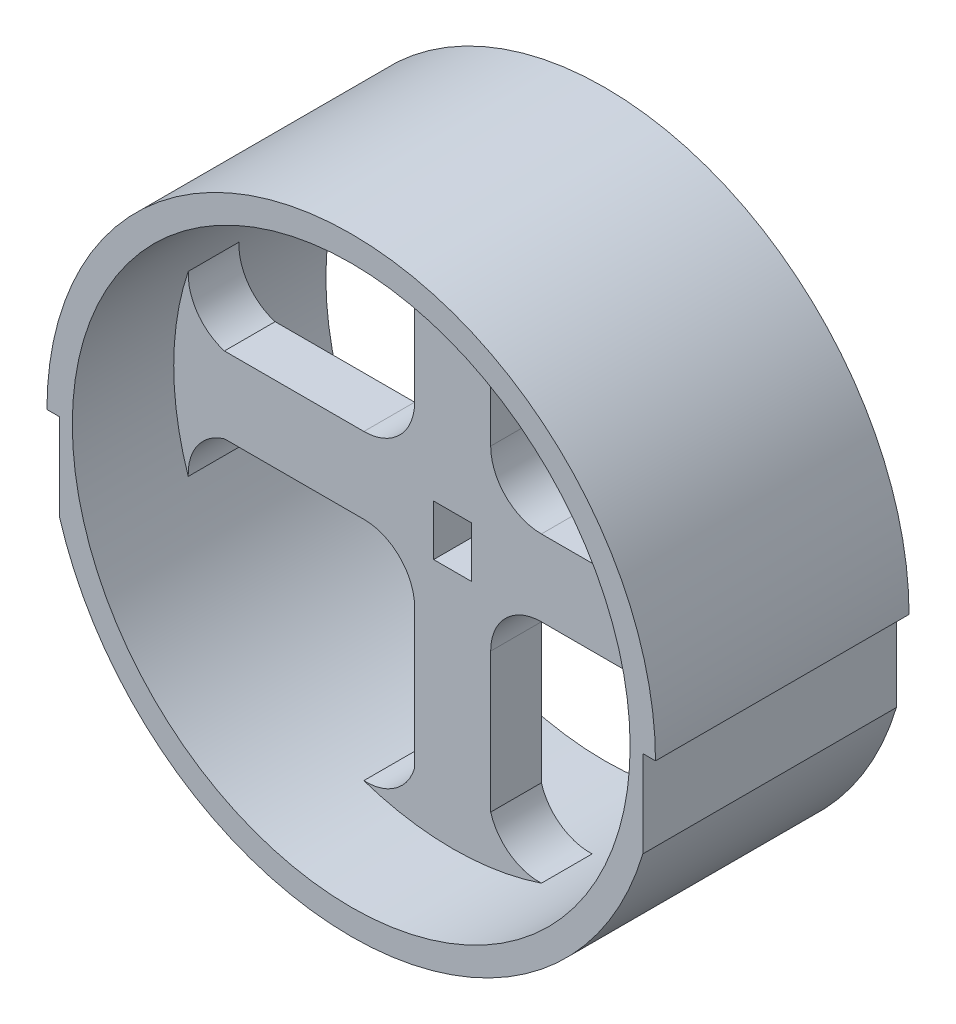
SolidWorks part; units mm, degrees
material "6061 Alloy"
ref_plane "Front Plane" through (0, 0, 0) normal (0, 0, 1) x (1, 0, 0)
ref_plane "Top Plane" through (0, 0, 0) normal (0, 1, 0) x (1, 0, 0)
ref_plane "Right Plane" through (0, 0, 0) normal (1, 0, 0) x (0, 0, -1)
sketch "Sketch1" plane through (0, 0, 0) normal (0, 0, 1) x (1, 0, 0)
  circle A0 centre (0, 0) radius 152.4
  circle A1 centre (0, 0) radius 139.7
  dimension "D1" = 304.8
  dimension "D2" = 279.4
extrude "Boss-Extrude1" add sketch "Sketch1" along normal mid plane 127
sketch "Sketch2" plane through (0, 0, 0) normal (0, 0, 1) x (1, 0, 0)
  line L0 (-114.3, 19.05) -> (-138.7192, 19.05)
  line L1 (-147.1918, -19.05) -> (147.1918, -19.05)
  line L2 (-147.1918, -19.05) -> (-147.1918, 19.05)
  line L3 (-147.1918, 19.05) -> (147.1918, 19.05)
  line L4 (147.1918, -19.05) -> (147.1918, 19.05)
  line L5 (-147.1918, -19.05) -> (147.1918, 19.05) construction
  line L6 (-147.1918, 19.05) -> (147.1918, -19.05) construction
  line L7 (19.05, -143.9568) -> (-19.05, -143.9568)
  line L8 (19.05, -143.9568) -> (19.05, 143.9568)
  line L9 (19.05, 143.9568) -> (-19.05, 143.9568)
  line L10 (-19.05, -143.9568) -> (-19.05, 143.9568)
  line L11 (19.05, -143.9568) -> (-19.05, 143.9568) construction
  line L12 (19.05, 143.9568) -> (-19.05, -143.9568) construction
  line L15 (-44.45, 19.05) -> (-19.05, 19.05)
  line L16 (-19.05, 44.45) -> (-19.05, 19.05)
  line L17 (-132.4254, 44.4927) -> (-143.3503, 19.05)
  line L18 (-143.3503, 19.05) -> (-138.7192, 19.05)
  line L19 (-138.7192, 19.05) -> (-143.3503, 19.05)
  line L20 (-19.05, 114.3) -> (-19.05, 143.9568)
  line L21 (-44.45, 132.4398) -> (-19.05, 143.9568)
  line L22 (44.45, 19.05) -> (19.05, 19.05)
  line L23 (19.05, 44.45) -> (19.05, 19.05)
  line L24 (19.05, 143.3503) -> (19.05, 138.7192)
  line L25 (19.05, 114.3) -> (19.05, 138.7192)
  line L26 (44.4927, 132.4254) -> (19.05, 143.3503)
  line L27 (114.3, 19.05) -> (143.9568, 19.05)
  line L28 (132.4398, 44.45) -> (143.9568, 19.05)
  line L29 (19.05, -44.45) -> (19.05, -19.05)
  line L30 (44.45, -19.05) -> (19.05, -19.05)
  line L31 (143.3503, -19.05) -> (138.7192, -19.05)
  line L32 (114.3, -19.05) -> (138.7192, -19.05)
  line L33 (132.4254, -44.4927) -> (143.3503, -19.05)
  line L34 (19.05, -114.3) -> (19.05, -143.9568)
  line L35 (44.45, -132.4398) -> (19.05, -143.9568)
  line L36 (-44.45, -19.05) -> (-19.05, -19.05)
  line L37 (-19.05, -44.45) -> (-19.05, -19.05)
  line L38 (-19.05, -143.3503) -> (-19.05, -138.7192)
  line L39 (-19.05, -114.3) -> (-19.05, -138.7192)
  line L40 (-44.4927, -132.4254) -> (-19.05, -143.3503)
  line L41 (-114.3, -19.05) -> (-143.9568, -19.05)
  line L42 (-132.4398, -44.45) -> (-143.9568, -19.05)
  arc A1 (-44.45, 19.05) -> (-19.05, 44.45) centre (-44.45, 44.45) ccw
  arc A2 (-114.3, 19.05) -> (-132.4254, 44.4927) centre (-107.0492, 43.3931) cw
  circle A3 centre (0, 0) radius 139.7 construction
  arc A5 (-19.05, 114.3) -> (-44.45, 132.4398) centre (-43.3968, 107.0616) ccw
  arc A6 (19.05, 44.45) -> (44.45, 19.05) centre (44.45, 44.45) ccw
  arc A7 (19.05, 114.3) -> (44.4927, 132.4254) centre (43.3931, 107.0492) cw
  arc A8 (114.3, 19.05) -> (132.4398, 44.45) centre (107.0616, 43.3968) ccw
  arc A9 (44.45, -19.05) -> (19.05, -44.45) centre (44.45, -44.45) ccw
  arc A10 (114.3, -19.05) -> (132.4254, -44.4927) centre (107.0492, -43.3931) cw
  arc A11 (19.05, -114.3) -> (44.45, -132.4398) centre (43.3968, -107.0616) ccw
  arc A12 (-19.05, -44.45) -> (-44.45, -19.05) centre (-44.45, -44.45) ccw
  arc A13 (-19.05, -114.3) -> (-44.4927, -132.4254) centre (-43.3931, -107.0492) cw
  arc A14 (-114.3, -19.05) -> (-132.4398, -44.45) centre (-107.0616, -43.3968) ccw
  point P0 (0, 0)
  point P6 (0, 0)
  point P67 (0, 0)
  dimension "D3" = 25.4
  dimension "D5" = 25.4
  dimension "D1" = 38.1
  dimension "D2" = 38.1
  dimension "D4" = 114.3
  dimension "D6" = 114.3
  dimension "D7" = 4
extrude "Boss-Extrude2" add sketch "Sketch2" along normal mid plane 25.4 contours L1 L10 L3 L2 | L10 L1 L8 L3 | L10 L3 L8 L9 | L8 L1 L4 L3 | L10 L7 L8 L1 | A14 L1 L42 | L10 A13 L40 | A11 L8 L35 | A9 L1 L8 | L1 A10 L33 | A8 L3 L28 | L8 A7 L26 | A5 L10 L21 | L0 A2 L17 L3 | A1 L3 L10 | A6 L8 L3 | A12 L10 L1 region at (-83.1209, 0, 0) region at (-132.2215, 26.1932, 0) region at (-24.7235, 24.7235, 0) region at (0, 81.5034, 0) region at (0, 0, 0) region at (24.7235, 24.7235, 0) region at (83.1209, 0, 0) region at (-24.7235, -24.7235, 0) region at (0, -81.5034, 0) region at (-26.2233, 132.4495, 0) region at (24.7235, -24.7235, 0) region at (-132.4495, -26.2233, 0) region at (132.4495, 26.2233, 0) region at (26.1932, 132.2215, 0) region at (-26.1932, -132.2215, 0) region at (132.2215, -26.1932, 0) region at (26.2233, -132.4495, 0)
sketch "Sketch4" plane through (0, 0, 0) normal (0, 0, 1) x (1, 0, 0)
  line L0 (-9.525, -19.05) -> (-9.525, 0)
  line L5 (-9.525, -19.05) -> (9.525, -19.05)
  line L6 (-9.525, 0) -> (9.525, 0)
  line L7 (9.525, -19.05) -> (9.525, 0)
  line L8 (-9.525, -19.05) -> (9.525, 0) construction
  line L9 (-9.525, 0) -> (9.525, -19.05) construction
  point P1 (0, -9.525)
  dimension "D1" = 19.05
  dimension "D2" = 19.05
  dimension "D3" = 9.525
  dimension "D4" = 0
extrude "Cut-Extrude3" cut sketch "Sketch4" against normal through all both and the other way through all
sketch "Sketch7" plane through (0, 0, 12.7) normal (0, 0, 1) x (1, 0, 0)
  line L0 (-9.525, 0) -> (9.525, 0)
  line L1 (-9.525, 0) -> (-9.525, 6.35)
  line L2 (9.525, 0) -> (9.525, 6.35)
  line L3 (-9.525, 6.35) -> (9.525, 6.35)
  line L4 (9.525, 0) -> (-9.525, 0) construction
  line L5 (-9.525, -19.05) -> (9.525, -19.05) construction
  dimension "D1" = 25.4
extrude "Cut-Extrude4" cut sketch "Sketch7" against normal through all
sketch "Sketch8" plane through (0, 0, 63.5) normal (0, 0, 1) x (1, 0, 0)
  line L0 (-146.05, 0) -> (-163.2527, 0)
  line L1 (-146.05, 0) -> (-146.05, -50.8)
  line L2 (-163.2527, 0) -> (-163.2527, -50.8)
  line L3 (-146.05, -50.8) -> (-163.2527, -50.8)
  circle A0 centre (0, 0) radius 152.4 construction
  dimension "D1" = 50.8
  dimension "D2" = 146.05
extrude "Cut-Extrude5" cut sketch "Sketch8" against normal through all
mirror "Mirror1" about plane through (0, 0, 0) normal (1, 0, 0) of "Cut-Extrude5"
